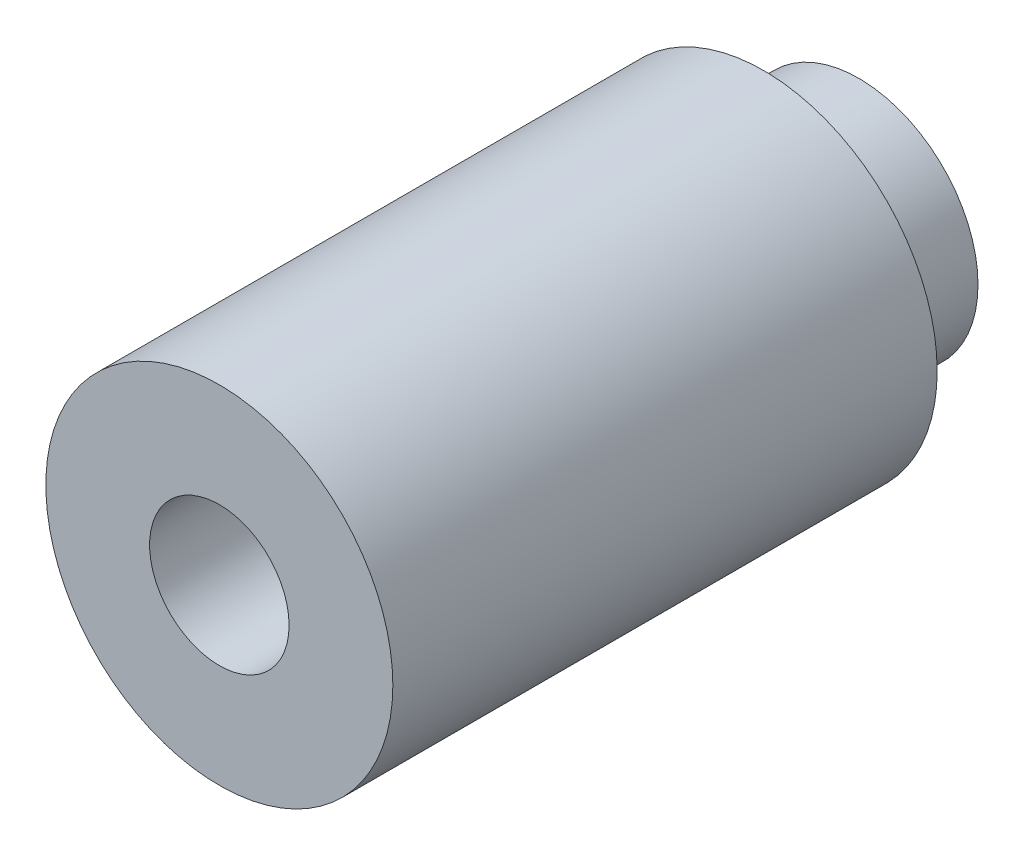
SolidWorks part; units mm, degrees
material "Plain Carbon Steel"
ref_plane "Front Plane" through (0, 0, 0) normal (0, 0, 1) x (1, 0, 0)
ref_plane "Top Plane" through (0, 0, 0) normal (0, 1, 0) x (1, 0, 0)
ref_plane "Right Plane" through (0, 0, 0) normal (1, 0, 0) x (0, 0, -1)
sketch "main_features" plane through (0, 0, 0) normal (0, 0, 1) x (1, 0, 0)
  circle A0 centre (0, 0) radius 2.55
  circle A1 centre (0, 0) radius 1.75
  dimension "D1" = 5.1
  dimension "D2" = 3.5
extrude "body" add sketch "main_features" along normal blind 8 contours A0
extrude "peg" add sketch "Sketch1<3>" against normal blind 1.4 contours A1 region at (0, 0, 0)
sketch "Sketch1<3>" plane through (0, 0, 0) normal (0, 0, 1) x (1, 0, 0) same geometry as "main_features"
hole_wizard "M2.5x0.45 Tapped Hole1" positions "Sketch2" profile "Sketch3" tap size "M2.5x0.45" standard "ANSI Metric" end condition up to next
sketch "Sketch2" plane through (0, 0, 8) normal (0, 0, 1) x (1, 0, 0)
  point P0 (0, 0)
sketch "Sketch3" plane through (0, 0, 8) normal (1, 0, 0) x (0, -1, 0)
  line L0 (0, 0) -> (0, 9.4)
  line L1 (0, 9.4) -> (1.025, 9.4)
  line L2 (1.025, 9.4) -> (1.025, 0)
  line L5 (1.025, 0) -> (0, 0)
  line L11 (0, -6.35) -> (0, 107.95) construction
  dimension "Thru Tap Drill Dia." = 2.05
  dimension "Thru Tap Drill Depth" = 9.4
cosmetic thread "Hole Thread1" parameters "D2"=2.5
